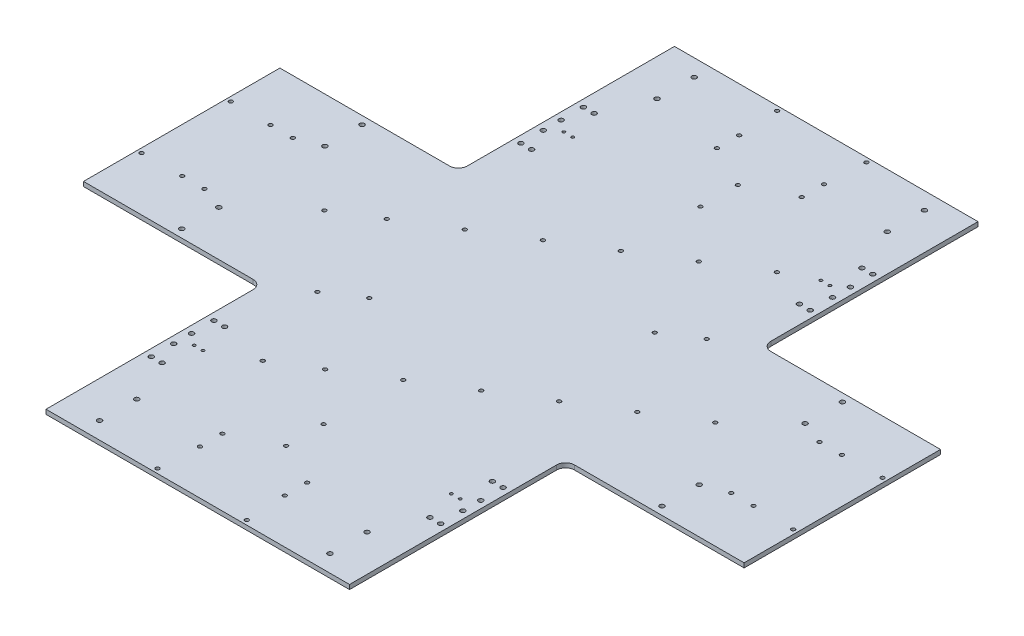
SolidWorks part; units mm, degrees
material "3.0205 (EN-AW 1200)"
ref_plane "前视基准面" through (0, 0, 0) normal (0, 0, 1) x (1, 0, 0)
ref_plane "上视基准面" through (0, 0, 0) normal (0, 1, 0) x (1, 0, 0)
ref_plane "右视基准面" through (0, 0, 0) normal (1, 0, 0) x (0, 0, -1)
other "Configuration Table"
sketch "Sketch1" plane through (0, 0, 0) normal (0, 1, 0) x (1, 0, 0)
  line L0 (170, 352) -> (-170, 352)
  line L1 (-170, 352) -> (-170, 110)
  line L2 (-170, 110) -> (-370, 110)
  line L5 (-370, 110) -> (-370, -110)
  line L6 (0, 352) -> (0, -66.8675) construction
  line L7 (-370, 0) -> (131.0517, 0) construction
  line L8 (370, 110) -> (370, -110)
  line L11 (170, 110) -> (370, 110)
  line L12 (170, 352) -> (170, 110)
  line L13 (170, -352) -> (170, -110)
  line L14 (170, -110) -> (370, -110)
  line L19 (-170, -110) -> (-370, -110)
  line L20 (-170, -352) -> (-170, -110)
  line L21 (170, -352) -> (-170, -352)
  point P21 (370, 0)
  dimension "D1" = 170
  dimension "D2" = 200
  dimension "D3" = 110
  dimension "D4" = 242
extrude "Boss-Extrude1" add sketch "Sketch1" along normal blind 5
sketch "Sketch2" plane through (0, 5, 0) normal (0, 1, 0) x (1, 0, 0)
  line L2 (370, 110) -> (170, 110) construction
  line L3 (370, -110) -> (370, 110) construction
  line L4 (-56.7455, 0) -> (47.5165, 0) construction
  line L5 (0, 54.7142) -> (0, -64.2255) construction
  line L7 (170, 352) -> (-170, 352) construction
  circle A0 centre (320, 49.5) radius 2.125
  circle A1 centre (295, 49.5) radius 2.125
  circle A7 centre (295, -49.5) radius 2.125
  circle A8 centre (320, -49.5) radius 2.125
  circle A9 centre (-320, -49.5) radius 2.125
  circle A10 centre (-295, -49.5) radius 2.125
  circle A13 centre (-295, 49.5) radius 2.125
  circle A14 centre (-320, 49.5) radius 2.125
  circle A15 centre (47.5, 302) radius 2.125
  circle A16 centre (47.5, 277) radius 2.125
  circle A17 centre (-47.5, 277) radius 2.125
  circle A18 centre (-47.5, 302) radius 2.125
  circle A19 centre (-47.5, -302) radius 2.125
  circle A20 centre (-47.5, -277) radius 2.125
  circle A21 centre (47.5, -277) radius 2.125
  circle A22 centre (47.5, -302) radius 2.125
  dimension "D1" = 60.5
  dimension "D5" = 4.25
  dimension "D7" = 4.25
  dimension "D9" = 4.25
  dimension "D10" = 4.25
  dimension "D4" = 25
  dimension "D6" = 50
  dimension "D11" = 47.5
  dimension "D12" = 50
  dimension "D13" = 25
extrude "Cut-Extrude1" cut sketch "Sketch2" against normal blind 3
sketch "Sketch4" plane through (0, 5, 0) normal (0, 1, 0) x (1, 0, 0)
  line L0 (-170, 352) -> (-170, 110) construction
  line L1 (170, 352) -> (-170, 352) construction
  line L2 (0, 46.9886) -> (0, -40.2904) construction
  line L3 (-35.103, 0) -> (92.4951, 0) construction
  line L5 (170, -352) -> (170, -110) construction
  circle A0 centre (-162, 172) radius 2.6
  circle A1 centre (-150, 172) radius 2.6
  circle A2 centre (-162, 197) radius 2.6
  circle A3 centre (-162, 217) radius 2.6
  circle A4 centre (-162, 242) radius 2.6
  circle A5 centre (-150, 242) radius 2.6
  circle A6 centre (150, 242) radius 2.6
  circle A7 centre (162, 242) radius 2.6
  circle A8 centre (162, 217) radius 2.6
  circle A9 centre (162, 197) radius 2.6
  circle A10 centre (150, 172) radius 2.6
  circle A11 centre (162, 172) radius 2.6
  circle A12 centre (162, -172) radius 2.6
  circle A13 centre (150, -172) radius 2.6
  circle A14 centre (162, -197) radius 2.6
  circle A15 centre (162, -217) radius 2.6
  circle A16 centre (162, -242) radius 2.6
  circle A17 centre (150, -242) radius 2.6
  circle A18 centre (-150, -242) radius 2.6
  circle A19 centre (-162, -242) radius 2.6
  circle A20 centre (-162, -217) radius 2.6
  circle A21 centre (-162, -197) radius 2.6
  circle A22 centre (-150, -172) radius 2.6
  circle A23 centre (-162, -172) radius 2.6
  circle A24 centre (149, -207) radius 1.6
  circle A25 centre (-149, -207) radius 1.6
  circle A26 centre (149, 207) radius 1.6
  circle A27 centre (-149, 207) radius 1.6
  circle A28 centre (139, -207) radius 1.6
  circle A29 centre (-139, -207) radius 1.6
  circle A30 centre (139, 207) radius 1.6
  circle A31 centre (-139, 207) radius 1.6
  dimension "D3" = 5.2
  dimension "D4" = 5.2
  dimension "D5" = 8
  dimension "D6" = 8
  dimension "D9" = 5.2
  dimension "D10" = 5.2
  dimension "D11" = 5.2
  dimension "D12" = 5.2
  dimension "D19" = 3.2
  dimension "D20" = 21
  dimension "D21" = 10
  dimension "D22" = 3.2
  dimension "D23" = 10
  dimension "D1" = 8
  dimension "D2" = 20
  dimension "D7" = 8
  dimension "D8" = 20
  dimension "D13" = 25
  dimension "D14" = 20
  dimension "D15" = 25
  dimension "D16" = 25
  dimension "D17" = 110
  dimension "D18" = 0
extrude "Cut-Extrude3" cut sketch "Sketch4" against normal blind 10
sketch "Sketch5" plane through (0, 5, 0) normal (0, 1, 0) x (1, 0, 0)
  line L0 (170, 352) -> (-170, 352) construction
  line L5 (-46.9195, 0) -> (66.6223, 0) construction
  line L6 (0, 59.0569) -> (0, -54.4849) construction
  line L10 (-370, 110) -> (-370, -110) construction
  line L12 (-170, 110) -> (-370, 110) construction
  line L13 (-370, -110) -> (-170, -110) construction
  circle A0 centre (-50, 347) radius 2.125
  circle A1 centre (50, 347) radius 2.125
  circle A2 centre (50, -347) radius 2.125
  circle A3 centre (-50, -347) radius 2.125
  circle A4 centre (-365, 50) radius 2.125
  circle A5 centre (-365, -50) radius 2.125
  circle A6 centre (365, -50) radius 2.125
  circle A7 centre (365, 50) radius 2.125
  dimension "D1" = 4.25
  dimension "D2" = 4.25
  dimension "D3" = 60
  dimension "D6" = 4.25
  dimension "D7" = 4.25
  dimension "5" = 5
  dimension "D4" = 50
  dimension "D5" = 50
  dimension "D8" = 60
  dimension "D9" = 5
  dimension "D10" = 5
extrude "Cut-Extrude4" cut sketch "Sketch5" against normal blind 10
fillet "Fillet1" radius 10 4 edges at (-170, 2.5, -110) (-170, 2.5, 110) (170, 2.5, 110) (170, 2.5, -110)
sketch "Sketch6" plane through (0, 5, 0) normal (0, 1, 0) x (1, 0, 0)
  line L0 (170, 352) -> (-170, 352) construction
  line L2 (170, 120) -> (170, 352) construction
  line L3 (-64.416, 0) -> (103.2752, 0) construction
  line L4 (0, 86.0771) -> (0, -73.7041) construction
  line L5 (370, 110) -> (180, 110) construction
  line L6 (370, -110) -> (370, 110) construction
  circle A0 centre (129, 333) radius 2.6
  circle A1 centre (129, 291.4) radius 2.6
  circle A2 centre (129, -291.4) radius 2.6
  circle A3 centre (129, -333) radius 2.6
  circle A4 centre (-129, -333) radius 2.6
  circle A5 centre (-129, -291.4) radius 2.6
  circle A6 centre (-129, 291.4) radius 2.6
  circle A7 centre (-129, 333) radius 2.6
  circle A8 centre (269, 101) radius 2.6
  circle A9 centre (269, 59.4) radius 2.6
  circle A10 centre (269, -59.4) radius 2.6
  circle A11 centre (269, -101) radius 2.6
  circle A12 centre (-269, -101) radius 2.6
  circle A13 centre (-269, -59.4) radius 2.6
  circle A14 centre (-269, 59.4) radius 2.6
  circle A15 centre (-269, 101) radius 2.6
  dimension "D1" = 5.2
  dimension "D2" = 5.2
  dimension "D6" = 5.2
  dimension "D7" = 5.2
  dimension "D3" = 19
  dimension "D4" = 41
  dimension "D5" = 41.6
  dimension "D8" = 9
  dimension "D9" = 41.6
  dimension "D10" = 101
extrude "Cut-Extrude5" cut sketch "Sketch6" against normal blind 10
sketch "Sketch7" plane through (0, 5, 0) normal (0, 1, 0) x (1, 0, 0)
  line L0 (197.463, 121.9013) -> (-168.3949, -103.9565) construction
  line L1 (180, 235.6925) -> (-379.973, -110) construction
  line L2 (144.6063, 226.5583) -> (333.7962, -79.9026) construction
  line L3 (-55.682, 90.1971) -> (55.682, -90.1971) construction
  line L4 (-172.9289, -112.9289) -> (172.9289, 112.9289) construction
  circle A0 centre (-55.682, 90.1971) radius 2.125
  circle A1 centre (-1.6489, 123.5538) radius 2.125
  circle A2 centre (52.3842, 156.9105) radius 2.125
  circle A3 centre (106.4174, 190.2672) radius 2.125
  circle A4 centre (-109.7152, 56.8404) radius 2.125
  circle A5 centre (-163.7483, 23.4837) radius 2.125
  circle A6 centre (-206.9749, -3.2017) radius 2.125
  circle A7 centre (-95.6108, -183.5958) radius 2.125
  circle A8 centre (-52.3842, -156.9105) radius 2.125
  circle A9 centre (1.6489, -123.5538) radius 2.125
  circle A10 centre (217.7815, 9.873) radius 2.125
  circle A11 centre (163.7483, -23.4837) radius 2.125
  circle A12 centre (109.7152, -56.8404) radius 2.125
  circle A13 centre (55.682, -90.1971) radius 2.125
  arc A14 (170, 120) -> (180, 110) centre (180, 120) ccw construction
  arc A15 (-170, -120) -> (-180, -110) centre (-180, -120) ccw construction
  point P35 (0, 0)
  point P36 (172.9289, 112.9289)
  point P37 (-172.9289, -112.9289)
  dimension "D1" = 4.25
  dimension "D2" = 4.25
  dimension "D3" = 4.25
  dimension "4.25" = 4.25
  dimension "D5" = 4.25
  dimension "D6" = 4.25
  dimension "D7" = 4.25
  dimension "D8" = 63.5
  dimension "D9" = 63.5
  dimension "D10" = 50.8
  dimension "D11" = 63.5
  dimension "D12" = 63.5
  dimension "D13" = 63.5
  dimension "D14" = 0
  dimension "D15" = 0
  dimension "D16" = 106
extrude "Cut-Extrude6" cut sketch "Sketch7" against normal blind 10
sketch "Sketch8" plane through (0, 5, 0) normal (0, 1, 0) x (1, 0, 0)
  line L0 (172.9289, 112.9289) -> (-172.9289, -112.9289) construction
  line L1 (85.2382, 119.1869) -> (148.2091, 22.7591) construction
  line L2 (-138.7195, -37.2906) -> (-84.6149, -120.1414) construction
  line L3 (0, 77.1364) -> (0, -65.7088) construction
  line L4 (-60.3124, 0) -> (69.2005, 0) construction
  line L5 (170, 352) -> (-170, 352) construction
  arc A0 (170, 120) -> (180, 110) centre (180, 120) ccw construction
  arc A1 (-170, -120) -> (-180, -110) centre (-180, -120) ccw construction
  circle A2 centre (-131.9022, -86.137) radius 2.1
  circle A3 centre (-96.7365, -63.1725) radius 2.1
  circle A4 centre (96.7365, 63.1725) radius 2.1
  circle A5 centre (131.9022, 86.137) radius 2.1
  circle A6 centre (0, 253) radius 2.1
  circle A7 centre (0, 211) radius 2.1
  circle A8 centre (0, -211) radius 2.1
  circle A9 centre (0, -253) radius 2.1
  dimension "D3" = 4.2
  dimension "D4" = 4.2
  dimension "D5" = 4.2
  dimension "D6" = 4.2
  dimension "D8" = 21
  dimension "D11" = 4.2
  dimension "D12" = 4.2
  dimension "D1" = 70
  dimension "D2" = 70
  dimension "D7" = 21
  dimension "D9" = 21
  dimension "D10" = 21
  dimension "D13" = 99
  dimension "D14" = 42
extrude "Cut-Extrude7" cut sketch "Sketch8" against normal blind 10
